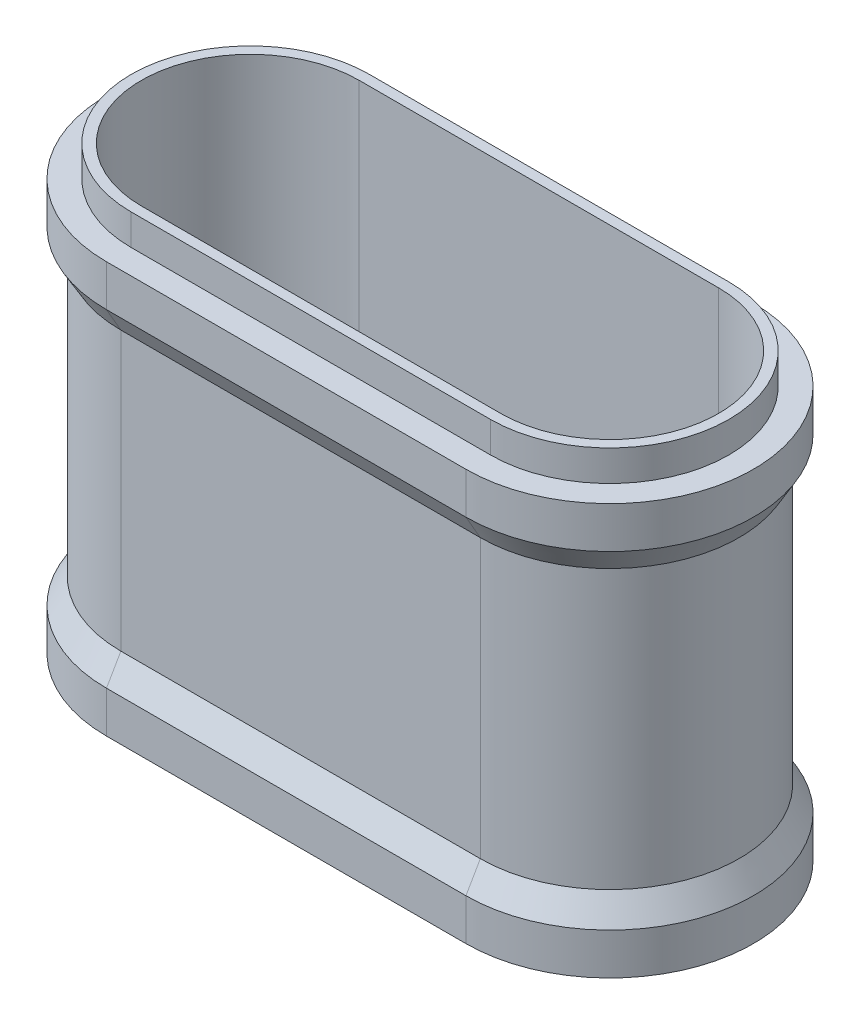
SolidWorks part; units mm, degrees
ref_plane "Front Plane" through (0, 0, 0) normal (0, 0, 1) x (1, 0, 0)
ref_plane "Top Plane" through (0, 0, 0) normal (0, 1, 0) x (1, 0, 0)
ref_plane "Right Plane" through (0, 0, 0) normal (1, 0, 0) x (0, 0, -1)
sketch "Sketch1" plane through (0, 0, 0) normal (0, 1, 0) x (1, 0, 0)
  line L0 (-8.75, 0) -> (8.75, 0) construction
  line L1 (-8.75, 5.3) -> (8.75, 5.3)
  line L2 (-8.75, -5.3) -> (8.75, -5.3)
  line L3 (-8.75, 6.3) -> (8.75, 6.3)
  line L4 (-8.75, -6.3) -> (8.75, -6.3)
  arc A0 (-8.75, 5.3) -> (-8.75, -5.3) centre (-8.75, 0) ccw
  arc A1 (8.75, -5.3) -> (8.75, 5.3) centre (8.75, 0) ccw
  arc A2 (8.75, -6.3) -> (8.75, 6.3) centre (8.75, 0) ccw
  arc A3 (-8.75, 6.3) -> (-8.75, -6.3) centre (-8.75, 0) ccw
  point P2 (0, 0)
  dimension "D1" = 17.5
  dimension "D2" = 10.6
  dimension "D3" = 1
extrude "Boss-Extrude1" add sketch "Sketch1" along normal blind 10 and the other way blind 10
sketch "Sketch2" plane through (0, 10, 0) normal (0, 1, 0) x (1, 0, 0)
  line L0 (-8.75, -5.3) -> (8.75, -5.3) construction
  line L1 (8.75, 5.3) -> (-8.75, 5.3) construction
  line L2 (-8.75, -5.3) -> (8.75, -5.3)
  line L3 (8.75, 5.3) -> (-8.75, 5.3)
  line L4 (8.75, 0) -> (-8.75, 0) construction
  line L5 (8.75, -7) -> (-8.75, -7)
  line L6 (8.75, 7) -> (-8.75, 7)
  arc A1 (-8.75, 5.3) -> (-8.75, -5.3) centre (-8.75, 0) ccw construction
  arc A2 (8.75, -5.3) -> (8.75, 5.3) centre (8.75, 0) ccw construction
  arc A3 (-8.75, 5.3) -> (-8.75, -5.3) centre (-8.75, 0) ccw
  arc A4 (8.75, -5.3) -> (8.75, 5.3) centre (8.75, 0) ccw
  arc A5 (8.75, -7) -> (8.75, 7) centre (8.75, 0) ccw
  arc A6 (-8.75, 7) -> (-8.75, -7) centre (-8.75, 0) ccw
  point P6 (0, 0)
  dimension "D1" = 14
extrude "Boss-Extrude2" add sketch "Sketch2" against normal blind 1.5
mirror "Mirror1" about plane through (0, 0, 0) normal (0, 1, 0) of "Boss-Extrude2"
sketch "Sketch3" plane through (0, 10, 0) normal (0, 1, 0) x (1, 0, 0)
  line L0 (-8.75, -5.3) -> (8.75, -5.3) construction
  line L1 (8.75, 5.3) -> (-8.75, 5.3) construction
  line L2 (-8.75, -5.3) -> (8.75, -5.3)
  line L3 (8.75, 5.3) -> (-8.75, 5.3)
  line L4 (-8.75, -5.8) -> (8.75, -5.8)
  line L5 (8.75, 5.8) -> (-8.75, 5.8)
  arc A0 (8.75, -5.3) -> (8.75, 5.3) centre (8.75, 0) ccw construction
  arc A1 (-8.75, 5.3) -> (-8.75, -5.3) centre (-8.75, 0) ccw construction
  arc A2 (8.75, -5.3) -> (8.75, 5.3) centre (8.75, 0) ccw
  arc A3 (-8.75, 5.3) -> (-8.75, -5.3) centre (-8.75, 0) ccw
  arc A4 (8.75, -5.8) -> (8.75, 5.8) centre (8.75, 0) ccw
  arc A5 (-8.75, 5.8) -> (-8.75, -5.8) centre (-8.75, 0) ccw
  dimension "D1" = 0.5
extrude "Boss-Extrude3" add sketch "Sketch3" along normal blind 1.5
chamfer "Chamfer1" distance 1 angle 60 8 edges at (15.05, -8.5, 0) (0, -8.5, -6.3) (0, -8.5, 6.3) (-15.05, -8.5, 0) (0, 8.5, -6.3) (15.05, 8.5, 0) (-15.05, 8.5, 0) (0, 8.5, 6.3) first distance on face at (0, -8.5, 0) first distance on face at (0, 8.5, 0)
